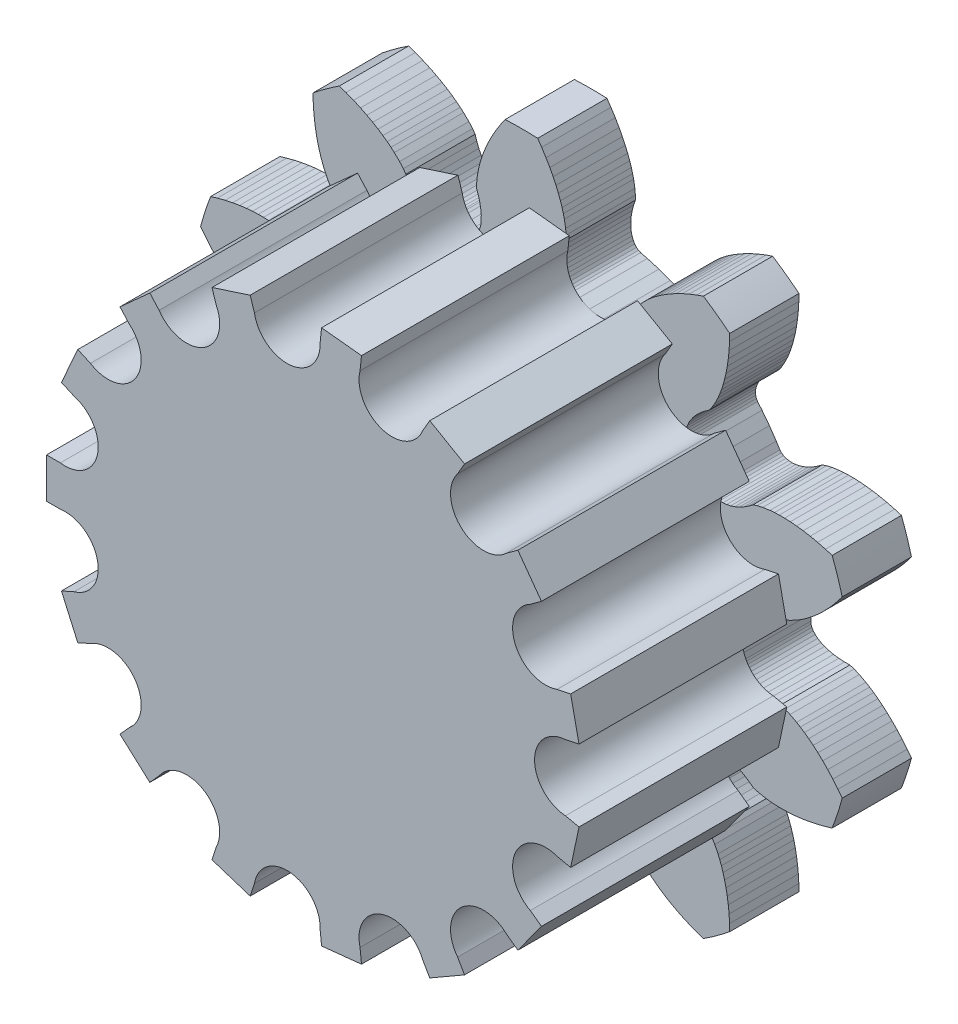
SolidWorks part; units mm, degrees
ref_plane "Front Plane" through (0, 0, 0) normal (0, 0, 1) x (1, 0, 0)
ref_plane "Top Plane" through (0, 0, 0) normal (0, 1, 0) x (1, 0, 0)
ref_plane "Right Plane" through (0, 0, 0) normal (1, 0, 0) x (0, 0, -1)
sketch "Model" plane through (0, 0, 0) normal (0, 0, 1) x (1, 0, 0)
  line L0 (44.9714, -18.1936) -> (45.0072, -17.6135)
  line L1 (45.0072, -17.6135) -> (45.064, -17.0676)
  line L2 (45.064, -17.0676) -> (45.1386, -16.5586)
  line L3 (45.1386, -16.5586) -> (45.2286, -16.0837)
  line L4 (45.2286, -16.0837) -> (45.3307, -15.6464)
  line L5 (45.3307, -15.6464) -> (45.4422, -15.245)
  line L6 (45.4422, -15.245) -> (45.5601, -14.8808)
  line L7 (45.5601, -14.8808) -> (45.6817, -14.5526)
  line L8 (45.6817, -14.5526) -> (45.8046, -14.2592)
  line L9 (45.8046, -14.2592) -> (46.0415, -13.7787)
  line L10 (46.0415, -13.7787) -> (46.2493, -13.433)
  line L11 (46.2493, -13.433) -> (46.4387, -13.1745)
  line L12 (46.4387, -13.1745) -> (46.7566, -12.9496)
  line L13 (46.7566, -12.9496) -> (47.0768, -12.6883)
  line L14 (47.0768, -12.6883) -> (47.3522, -12.4243)
  line L15 (47.3522, -12.4243) -> (47.5834, -12.1609)
  line L16 (47.5834, -12.1609) -> (47.7708, -11.9014)
  line L17 (47.7708, -11.9014) -> (47.9153, -11.6488)
  line L18 (47.9153, -11.6488) -> (48.0178, -11.4063)
  line L19 (48.0178, -11.4063) -> (48.0795, -11.177)
  line L20 (48.0795, -11.177) -> (48.1017, -10.9637)
  line L21 (48.1017, -10.9637) -> (48.086, -10.7695)
  line L22 (48.086, -10.7695) -> (48.034, -10.597)
  line L23 (48.034, -10.597) -> (47.9475, -10.4489)
  line L24 (47.9475, -10.4489) -> (47.6302, -10.0694)
  line L25 (47.6302, -10.0694) -> (47.0962, -9.3752)
  line L26 (47.0962, -9.3752) -> (46.601, -8.6528)
  line L27 (46.601, -8.6528) -> (46.3381, -8.2337)
  line L28 (46.3381, -8.2337) -> (46.224, -8.1057)
  line L29 (46.224, -8.1057) -> (46.076, -8.0029)
  line L30 (46.076, -8.0029) -> (45.8961, -7.9279)
  line L31 (45.8961, -7.9279) -> (45.6864, -7.8832)
  line L32 (45.6864, -7.8832) -> (45.4493, -7.871)
  line L33 (45.4493, -7.871) -> (45.187, -7.8936)
  line L34 (45.187, -7.8936) -> (44.9021, -7.9529)
  line L35 (44.9021, -7.9529) -> (44.5973, -8.051)
  line L36 (44.5973, -8.051) -> (44.2754, -8.1894)
  line L37 (44.2754, -8.1894) -> (43.9392, -8.3698)
  line L38 (43.9392, -8.3698) -> (43.5918, -8.5936)
  line L39 (43.5918, -8.5936) -> (43.2796, -8.8264)
  line L40 (43.2796, -8.8264) -> (42.9752, -8.9266)
  line L41 (42.9752, -8.9266) -> (42.5822, -9.0175)
  line L42 (42.5822, -9.0175) -> (42.052, -9.0943)
  line L43 (42.052, -9.0943) -> (41.735, -9.1205)
  line L44 (41.735, -9.1205) -> (41.3854, -9.1348)
  line L45 (41.3854, -9.1348) -> (41.0026, -9.1343)
  line L46 (41.0026, -9.1343) -> (40.5863, -9.1164)
  line L47 (40.5863, -9.1164) -> (40.1389, -9.0783)
  line L48 (40.1389, -9.0783) -> (39.6594, -9.0172)
  line L49 (39.6594, -9.0172) -> (39.1523, -8.9308)
  line L50 (39.1523, -8.9308) -> (38.6155, -8.8161)
  line L51 (38.6155, -8.8161) -> (38.0528, -8.671)
  line L52 (38.0528, -8.671) -> (37.565, -8.5243)
  line L53 (36.8392, -6.2906) -> (37.1476, -5.8853)
  line L54 (37.1476, -5.8853) -> (37.5176, -5.4371)
  line L55 (37.5176, -5.4371) -> (37.8845, -5.0288)
  line L56 (37.8845, -5.0288) -> (38.244, -4.6608)
  line L57 (38.244, -4.6608) -> (38.596, -4.3295)
  line L58 (38.596, -4.3295) -> (38.9355, -4.0358)
  line L59 (38.9355, -4.0358) -> (39.2618, -3.7766)
  line L60 (39.2618, -3.7766) -> (39.5712, -3.5512)
  line L61 (39.5712, -3.5512) -> (39.8624, -3.3572)
  line L62 (39.8624, -3.3572) -> (40.1343, -3.1921)
  line L63 (40.1343, -3.1921) -> (40.6084, -2.9426)
  line L64 (40.6084, -2.9426) -> (40.9797, -2.7851)
  line L65 (40.9797, -2.7851) -> (41.2849, -2.6873)
  line L66 (41.2849, -2.6873) -> (41.6743, -2.6921)
  line L67 (41.6743, -2.6921) -> (42.0869, -2.669)
  line L68 (42.0869, -2.669) -> (42.4649, -2.6173)
  line L69 (42.4649, -2.6173) -> (42.8067, -2.5401)
  line L70 (42.8067, -2.5401) -> (43.1109, -2.4403)
  line L71 (43.1109, -2.4403) -> (43.3763, -2.3209)
  line L72 (43.3763, -2.3209) -> (43.6018, -2.1849)
  line L73 (43.6018, -2.1849) -> (43.7865, -2.0357)
  line L74 (43.7865, -2.0357) -> (43.9298, -1.8762)
  line L75 (43.9298, -1.8762) -> (44.0312, -1.7098)
  line L76 (44.0312, -1.7098) -> (44.0905, -1.5397)
  line L77 (44.0905, -1.5397) -> (44.1076, -1.369)
  line L78 (44.1076, -1.369) -> (44.074, -0.8755)
  line L79 (44.074, -0.8755) -> (44.05, 0)
  line L80 (44.05, 0) -> (44.074, 0.8755)
  line L81 (44.074, 0.8755) -> (44.1076, 1.369)
  line L82 (44.1076, 1.369) -> (44.0905, 1.5397)
  line L83 (44.0905, 1.5397) -> (44.0312, 1.7098)
  line L84 (44.0312, 1.7098) -> (43.9298, 1.8762)
  line L85 (43.9298, 1.8762) -> (43.7865, 2.0357)
  line L86 (43.7865, 2.0357) -> (43.6018, 2.1849)
  line L87 (43.6018, 2.1849) -> (43.3763, 2.3209)
  line L88 (43.3763, 2.3209) -> (43.1109, 2.4403)
  line L89 (43.1109, 2.4403) -> (42.8067, 2.5401)
  line L90 (42.8067, 2.5401) -> (42.4649, 2.6173)
  line L91 (42.4649, 2.6173) -> (42.0869, 2.669)
  line L92 (42.0869, 2.669) -> (41.6743, 2.6921)
  line L93 (41.6743, 2.6921) -> (41.2849, 2.6873)
  line L94 (41.2849, 2.6873) -> (40.9797, 2.7851)
  line L95 (40.9797, 2.7851) -> (40.6084, 2.9426)
  line L96 (40.6084, 2.9426) -> (40.1343, 3.1921)
  line L97 (40.1343, 3.1921) -> (39.8624, 3.3572)
  line L98 (39.8624, 3.3572) -> (39.5712, 3.5512)
  line L99 (39.5712, 3.5512) -> (39.2618, 3.7766)
  line L100 (39.2618, 3.7766) -> (38.9355, 4.0358)
  line L101 (38.9355, 4.0358) -> (38.596, 4.3295)
  line L102 (38.596, 4.3295) -> (38.244, 4.6608)
  line L103 (38.244, 4.6608) -> (37.8845, 5.0288)
  line L104 (37.8845, 5.0288) -> (37.5176, 5.4371)
  line L105 (37.5176, 5.4371) -> (37.1476, 5.8853)
  line L106 (37.1476, 5.8853) -> (36.8392, 6.2906)
  line L107 (37.565, 8.5243) -> (38.0528, 8.671)
  line L108 (38.0528, 8.671) -> (38.6155, 8.8161)
  line L109 (38.6155, 8.8161) -> (39.1523, 8.9308)
  line L110 (39.1523, 8.9308) -> (39.6594, 9.0172)
  line L111 (39.6594, 9.0172) -> (40.1389, 9.0783)
  line L112 (40.1389, 9.0783) -> (40.5863, 9.1164)
  line L113 (40.5863, 9.1164) -> (41.0026, 9.1343)
  line L114 (41.0026, 9.1343) -> (41.3854, 9.1348)
  line L115 (41.3854, 9.1348) -> (41.735, 9.1205)
  line L116 (41.735, 9.1205) -> (42.052, 9.0943)
  line L117 (42.052, 9.0943) -> (42.5822, 9.0175)
  line L118 (42.5822, 9.0175) -> (42.9752, 8.9266)
  line L119 (42.9752, 8.9266) -> (43.2796, 8.8264)
  line L120 (43.2796, 8.8264) -> (43.5918, 8.5936)
  line L121 (43.5918, 8.5936) -> (43.9392, 8.3698)
  line L122 (43.9392, 8.3698) -> (44.2754, 8.1894)
  line L123 (44.2754, 8.1894) -> (44.5973, 8.051)
  line L124 (44.5973, 8.051) -> (44.9021, 7.9529)
  line L125 (44.9021, 7.9529) -> (45.187, 7.8936)
  line L126 (45.187, 7.8936) -> (45.4493, 7.871)
  line L127 (45.4493, 7.871) -> (45.6864, 7.8832)
  line L128 (45.6864, 7.8832) -> (45.8961, 7.9279)
  line L129 (45.8961, 7.9279) -> (46.076, 8.0029)
  line L130 (46.076, 8.0029) -> (46.224, 8.1057)
  line L131 (46.224, 8.1057) -> (46.3381, 8.2337)
  line L132 (46.3381, 8.2337) -> (46.601, 8.6528)
  line L133 (46.601, 8.6528) -> (47.0962, 9.3752)
  line L134 (47.0962, 9.3752) -> (47.6302, 10.0694)
  line L135 (47.6302, 10.0694) -> (47.9475, 10.4489)
  line L136 (47.9475, 10.4489) -> (48.034, 10.597)
  line L137 (48.034, 10.597) -> (48.086, 10.7695)
  line L138 (48.086, 10.7695) -> (48.1017, 10.9637)
  line L139 (48.1017, 10.9637) -> (48.0795, 11.177)
  line L140 (48.0795, 11.177) -> (48.0178, 11.4063)
  line L141 (48.0178, 11.4063) -> (47.9153, 11.6488)
  line L142 (47.9153, 11.6488) -> (47.7708, 11.9014)
  line L143 (47.7708, 11.9014) -> (47.5834, 12.1609)
  line L144 (47.5834, 12.1609) -> (47.3522, 12.4243)
  line L145 (47.3522, 12.4243) -> (47.0768, 12.6883)
  line L146 (47.0768, 12.6883) -> (46.7566, 12.9496)
  line L147 (46.7566, 12.9496) -> (46.4387, 13.1745)
  line L148 (46.4387, 13.1745) -> (46.2493, 13.433)
  line L149 (46.2493, 13.433) -> (46.0415, 13.7787)
  line L150 (46.0415, 13.7787) -> (45.8046, 14.2592)
  line L151 (45.8046, 14.2592) -> (45.6817, 14.5526)
  line L152 (45.6817, 14.5526) -> (45.5601, 14.8808)
  line L153 (45.5601, 14.8808) -> (45.4422, 15.245)
  line L154 (45.4422, 15.245) -> (45.3307, 15.6464)
  line L155 (45.3307, 15.6464) -> (45.2286, 16.0837)
  line L156 (45.2286, 16.0837) -> (45.1386, 16.5586)
  line L157 (45.1386, 16.5586) -> (45.064, 17.0676)
  line L158 (45.064, 17.0676) -> (45.0072, 17.6135)
  line L159 (45.0072, 17.6135) -> (44.9714, 18.1936)
  line L160 (44.9714, 18.1936) -> (44.9601, 18.7028)
  line L161 (46.8602, 20.0833) -> (47.341, 19.9152)
  line L162 (47.341, 19.9152) -> (47.8816, 19.7019)
  line L163 (47.8816, 19.7019) -> (48.3833, 19.4792)
  line L164 (48.3833, 19.4792) -> (48.8443, 19.2509)
  line L165 (48.8443, 19.2509) -> (49.2681, 19.0186)
  line L166 (49.2681, 19.0186) -> (49.6525, 18.7864)
  line L167 (49.6525, 18.7864) -> (49.9998, 18.5562)
  line L168 (49.9998, 18.5562) -> (50.3097, 18.3316)
  line L169 (50.3097, 18.3316) -> (50.5842, 18.1146)
  line L170 (50.5842, 18.1146) -> (50.8253, 17.907)
  line L171 (50.8253, 17.907) -> (51.2091, 17.5332)
  line L172 (51.2091, 17.5332) -> (51.4736, 17.2287)
  line L173 (51.4736, 17.2287) -> (51.6609, 16.9687)
  line L174 (51.6609, 16.9687) -> (51.7767, 16.5968)
  line L175 (51.7767, 16.5968) -> (51.9262, 16.2116)
  line L176 (51.9262, 16.2116) -> (52.0921, 15.8681)
  line L177 (52.0921, 15.8681) -> (52.2712, 15.5668)
  line L178 (52.2712, 15.5668) -> (52.4601, 15.3084)
  line L179 (52.4601, 15.3084) -> (52.6557, 15.0929)
  line L180 (52.6557, 15.0929) -> (52.8547, 14.9205)
  line L181 (52.8547, 14.9205) -> (53.0537, 14.7909)
  line L182 (53.0537, 14.7909) -> (53.2496, 14.7039)
  line L183 (53.2496, 14.7039) -> (53.4392, 14.6588)
  line L184 (53.4392, 14.6588) -> (53.6194, 14.655)
  line L185 (53.6194, 14.655) -> (53.7869, 14.6915)
  line L186 (53.7869, 14.6915) -> (54.2459, 14.876)
  line L187 (54.2459, 14.876) -> (55.0712, 15.1694)
  line L188 (55.0712, 15.1694) -> (55.9113, 15.4171)
  line L189 (55.9113, 15.4171) -> (56.391, 15.5376)
  line L190 (56.391, 15.5376) -> (56.548, 15.6066)
  line L191 (56.548, 15.6066) -> (56.6915, 15.7156)
  line L192 (56.6915, 15.7156) -> (56.8184, 15.8635)
  line L193 (56.8184, 15.8635) -> (56.9258, 16.049)
  line L194 (56.9258, 16.049) -> (57.0107, 16.2708)
  line L195 (57.0107, 16.2708) -> (57.0703, 16.5273)
  line L196 (57.0703, 16.5273) -> (57.1018, 16.8165)
  line L197 (57.1018, 16.8165) -> (57.1028, 17.1367)
  line L198 (57.1028, 17.1367) -> (57.0706, 17.4857)
  line L199 (57.0706, 17.4857) -> (57.0029, 17.8611)
  line L200 (57.0029, 17.8611) -> (56.8974, 18.2607)
  line L201 (56.8974, 18.2607) -> (56.7725, 18.6296)
  line L202 (56.7725, 18.6296) -> (56.7712, 18.95)
  line L203 (56.7712, 18.95) -> (56.8063, 19.3518)
  line L204 (56.8063, 19.3518) -> (56.897, 19.8798)
  line L205 (56.897, 19.8798) -> (56.97, 20.1894)
  line L206 (56.97, 20.1894) -> (57.0646, 20.5264)
  line L207 (57.0646, 20.5264) -> (57.1833, 20.8903)
  line L208 (57.1833, 20.8903) -> (57.329, 21.2806)
  line L209 (57.329, 21.2806) -> (57.5034, 21.6944)
  line L210 (57.5034, 21.6944) -> (57.7097, 22.1315)
  line L211 (57.7097, 22.1315) -> (57.9486, 22.5871)
  line L212 (57.9486, 22.5871) -> (58.2236, 23.0622)
  line L213 (58.2236, 23.0622) -> (58.5355, 23.5525)
  line L214 (58.5355, 23.5525) -> (58.8257, 23.9711)
  line L215 (61.1743, 23.9711) -> (61.4645, 23.5525)
  line L216 (61.4645, 23.5525) -> (61.7764, 23.0622)
  line L217 (61.7764, 23.0622) -> (62.0514, 22.5871)
  line L218 (62.0514, 22.5871) -> (62.2903, 22.1315)
  line L219 (62.2903, 22.1315) -> (62.4966, 21.6944)
  line L220 (62.4966, 21.6944) -> (62.671, 21.2806)
  line L221 (62.671, 21.2806) -> (62.8167, 20.8903)
  line L222 (62.8167, 20.8903) -> (62.9354, 20.5264)
  line L223 (62.9354, 20.5264) -> (63.03, 20.1894)
  line L224 (63.03, 20.1894) -> (63.103, 19.8798)
  line L225 (63.103, 19.8798) -> (63.1937, 19.3518)
  line L226 (63.1937, 19.3518) -> (63.2288, 18.95)
  line L227 (63.2288, 18.95) -> (63.2275, 18.6296)
  line L228 (63.2275, 18.6296) -> (63.1026, 18.2607)
  line L229 (63.1026, 18.2607) -> (62.9971, 17.8611)
  line L230 (62.9971, 17.8611) -> (62.9294, 17.4857)
  line L231 (62.9294, 17.4857) -> (62.8972, 17.1367)
  line L232 (62.8972, 17.1367) -> (62.8982, 16.8165)
  line L233 (62.8982, 16.8165) -> (62.9297, 16.5273)
  line L234 (62.9297, 16.5273) -> (62.9893, 16.2708)
  line L235 (62.9893, 16.2708) -> (63.0742, 16.049)
  line L236 (63.0742, 16.049) -> (63.1816, 15.8635)
  line L237 (63.1816, 15.8635) -> (63.3085, 15.7156)
  line L238 (63.3085, 15.7156) -> (63.452, 15.6066)
  line L239 (63.452, 15.6066) -> (63.609, 15.5376)
  line L240 (63.609, 15.5376) -> (64.0887, 15.4171)
  line L241 (64.0887, 15.4171) -> (64.9288, 15.1694)
  line L242 (64.9288, 15.1694) -> (65.7541, 14.876)
  line L243 (65.7541, 14.876) -> (66.2131, 14.6915)
  line L244 (66.2131, 14.6915) -> (66.3806, 14.655)
  line L245 (66.3806, 14.655) -> (66.5608, 14.6588)
  line L246 (66.5608, 14.6588) -> (66.7504, 14.7039)
  line L247 (66.7504, 14.7039) -> (66.9463, 14.7909)
  line L248 (66.9463, 14.7909) -> (67.1453, 14.9205)
  line L249 (67.1453, 14.9205) -> (67.3443, 15.0929)
  line L250 (67.3443, 15.0929) -> (67.5399, 15.3084)
  line L251 (67.5399, 15.3084) -> (67.7288, 15.5668)
  line L252 (67.7288, 15.5668) -> (67.9079, 15.8681)
  line L253 (67.9079, 15.8681) -> (68.0738, 16.2116)
  line L254 (68.0738, 16.2116) -> (68.2233, 16.5968)
  line L255 (68.2233, 16.5968) -> (68.3391, 16.9687)
  line L256 (68.3391, 16.9687) -> (68.5264, 17.2287)
  line L257 (68.5264, 17.2287) -> (68.7909, 17.5332)
  line L258 (68.7909, 17.5332) -> (69.1747, 17.907)
  line L259 (69.1747, 17.907) -> (69.4158, 18.1146)
  line L260 (69.4158, 18.1146) -> (69.6903, 18.3316)
  line L261 (69.6903, 18.3316) -> (70.0002, 18.5562)
  line L262 (70.0002, 18.5562) -> (70.3475, 18.7864)
  line L263 (70.3475, 18.7864) -> (70.7319, 19.0186)
  line L264 (70.7319, 19.0186) -> (71.1557, 19.2509)
  line L265 (71.1557, 19.2509) -> (71.6167, 19.4792)
  line L266 (71.6167, 19.4792) -> (72.1184, 19.7019)
  line L267 (72.1184, 19.7019) -> (72.659, 19.9152)
  line L268 (72.659, 19.9152) -> (73.1398, 20.0833)
  line L269 (75.0399, 18.7028) -> (75.0286, 18.1936)
  line L270 (75.0286, 18.1936) -> (74.9928, 17.6135)
  line L271 (74.9928, 17.6135) -> (74.936, 17.0676)
  line L272 (74.936, 17.0676) -> (74.8614, 16.5586)
  line L273 (74.8614, 16.5586) -> (74.7714, 16.0837)
  line L274 (74.7714, 16.0837) -> (74.6693, 15.6464)
  line L275 (74.6693, 15.6464) -> (74.5578, 15.245)
  line L276 (74.5578, 15.245) -> (74.4399, 14.8808)
  line L277 (74.4399, 14.8808) -> (74.3183, 14.5526)
  line L278 (74.3183, 14.5526) -> (74.1954, 14.2592)
  line L279 (74.1954, 14.2592) -> (73.9585, 13.7787)
  line L280 (73.9585, 13.7787) -> (73.7507, 13.433)
  line L281 (73.7507, 13.433) -> (73.5613, 13.1745)
  line L282 (73.5613, 13.1745) -> (73.2434, 12.9496)
  line L283 (73.2434, 12.9496) -> (72.9232, 12.6883)
  line L284 (72.9232, 12.6883) -> (72.6478, 12.4243)
  line L285 (72.6478, 12.4243) -> (72.4166, 12.1609)
  line L286 (72.4166, 12.1609) -> (72.2292, 11.9014)
  line L287 (72.2292, 11.9014) -> (72.0847, 11.6488)
  line L288 (72.0847, 11.6488) -> (71.9822, 11.4063)
  line L289 (71.9822, 11.4063) -> (71.9205, 11.177)
  line L290 (71.9205, 11.177) -> (71.8983, 10.9637)
  line L291 (71.8983, 10.9637) -> (71.914, 10.7695)
  line L292 (71.914, 10.7695) -> (71.966, 10.597)
  line L293 (71.966, 10.597) -> (72.0525, 10.4489)
  line L294 (72.0525, 10.4489) -> (72.3698, 10.0694)
  line L295 (72.3698, 10.0694) -> (72.9038, 9.3752)
  line L296 (72.9038, 9.3752) -> (73.399, 8.6528)
  line L297 (73.399, 8.6528) -> (73.6619, 8.2337)
  line L298 (73.6619, 8.2337) -> (73.776, 8.1057)
  line L299 (73.776, 8.1057) -> (73.924, 8.0029)
  line L300 (73.924, 8.0029) -> (74.1039, 7.9279)
  line L301 (74.1039, 7.9279) -> (74.3136, 7.8832)
  line L302 (74.3136, 7.8832) -> (74.5507, 7.871)
  line L303 (74.5507, 7.871) -> (74.813, 7.8936)
  line L304 (74.813, 7.8936) -> (75.0979, 7.9529)
  line L305 (75.0979, 7.9529) -> (75.4027, 8.051)
  line L306 (75.4027, 8.051) -> (75.7246, 8.1894)
  line L307 (75.7246, 8.1894) -> (76.0608, 8.3698)
  line L308 (76.0608, 8.3698) -> (76.4082, 8.5936)
  line L309 (76.4082, 8.5936) -> (76.7204, 8.8264)
  line L310 (76.7204, 8.8264) -> (77.0248, 8.9266)
  line L311 (77.0248, 8.9266) -> (77.4178, 9.0175)
  line L312 (77.4178, 9.0175) -> (77.948, 9.0943)
  line L313 (77.948, 9.0943) -> (78.265, 9.1205)
  line L314 (78.265, 9.1205) -> (78.6146, 9.1348)
  line L315 (78.6146, 9.1348) -> (78.9974, 9.1343)
  line L316 (78.9974, 9.1343) -> (79.4137, 9.1164)
  line L317 (79.4137, 9.1164) -> (79.8611, 9.0783)
  line L318 (79.8611, 9.0783) -> (80.3406, 9.0172)
  line L319 (80.3406, 9.0172) -> (80.8477, 8.9308)
  line L320 (80.8477, 8.9308) -> (81.3845, 8.8161)
  line L321 (81.3845, 8.8161) -> (81.9472, 8.671)
  line L322 (81.9472, 8.671) -> (82.435, 8.5243)
  line L323 (83.1608, 6.2906) -> (82.8524, 5.8853)
  line L324 (82.8524, 5.8853) -> (82.4824, 5.4371)
  line L325 (82.4824, 5.4371) -> (82.1155, 5.0288)
  line L326 (82.1155, 5.0288) -> (81.756, 4.6608)
  line L327 (81.756, 4.6608) -> (81.4041, 4.3295)
  line L328 (81.4041, 4.3295) -> (81.0645, 4.0358)
  line L329 (81.0645, 4.0358) -> (80.7382, 3.7766)
  line L330 (80.7382, 3.7766) -> (80.4288, 3.5512)
  line L331 (80.4288, 3.5512) -> (80.1376, 3.3572)
  line L332 (80.1376, 3.3572) -> (79.8657, 3.1921)
  line L333 (79.8657, 3.1921) -> (79.3916, 2.9426)
  line L334 (79.3916, 2.9426) -> (79.0203, 2.7851)
  line L335 (79.0203, 2.7851) -> (78.7151, 2.6873)
  line L336 (78.7151, 2.6873) -> (78.3257, 2.6921)
  line L337 (78.3257, 2.6921) -> (77.9131, 2.669)
  line L338 (77.9131, 2.669) -> (77.5351, 2.6173)
  line L339 (77.5351, 2.6173) -> (77.1933, 2.5401)
  line L340 (77.1933, 2.5401) -> (76.8891, 2.4403)
  line L341 (76.8891, 2.4403) -> (76.6237, 2.3209)
  line L342 (76.6237, 2.3209) -> (76.3983, 2.1849)
  line L343 (76.3983, 2.1849) -> (76.2135, 2.0357)
  line L344 (76.2135, 2.0357) -> (76.0702, 1.8762)
  line L345 (76.0702, 1.8762) -> (75.9688, 1.7098)
  line L346 (75.9688, 1.7098) -> (75.9095, 1.5397)
  line L347 (75.9095, 1.5397) -> (75.8924, 1.369)
  line L348 (75.8924, 1.369) -> (75.926, 0.8755)
  line L349 (75.926, 0.8755) -> (75.95, 0)
  line L350 (75.95, 0) -> (75.926, -0.8755)
  line L351 (75.926, -0.8755) -> (75.8924, -1.369)
  line L352 (75.8924, -1.369) -> (75.9095, -1.5397)
  line L353 (75.9095, -1.5397) -> (75.9688, -1.7098)
  line L354 (75.9688, -1.7098) -> (76.0702, -1.8762)
  line L355 (76.0702, -1.8762) -> (76.2135, -2.0357)
  line L356 (76.2135, -2.0357) -> (76.3983, -2.1849)
  line L357 (76.3983, -2.1849) -> (76.6237, -2.3209)
  line L358 (76.6237, -2.3209) -> (76.8891, -2.4403)
  line L359 (76.8891, -2.4403) -> (77.1933, -2.5401)
  line L360 (77.1933, -2.5401) -> (77.5351, -2.6173)
  line L361 (77.5351, -2.6173) -> (77.9131, -2.669)
  line L362 (77.9131, -2.669) -> (78.3257, -2.6921)
  line L363 (78.3257, -2.6921) -> (78.7151, -2.6873)
  line L364 (78.7151, -2.6873) -> (79.0203, -2.7851)
  line L365 (79.0203, -2.7851) -> (79.3916, -2.9426)
  line L366 (79.3916, -2.9426) -> (79.8657, -3.1921)
  line L367 (79.8657, -3.1921) -> (80.1376, -3.3572)
  line L368 (80.1376, -3.3572) -> (80.4288, -3.5512)
  line L369 (80.4288, -3.5512) -> (80.7382, -3.7766)
  line L370 (80.7382, -3.7766) -> (81.0645, -4.0358)
  line L371 (81.0645, -4.0358) -> (81.4041, -4.3295)
  line L372 (81.4041, -4.3295) -> (81.756, -4.6608)
  line L373 (81.756, -4.6608) -> (82.1155, -5.0288)
  line L374 (82.1155, -5.0288) -> (82.4824, -5.4371)
  line L375 (82.4824, -5.4371) -> (82.8524, -5.8853)
  line L376 (82.8524, -5.8853) -> (83.1608, -6.2906)
  line L377 (82.435, -8.5243) -> (81.9472, -8.671)
  line L378 (81.9472, -8.671) -> (81.3845, -8.8161)
  line L379 (81.3845, -8.8161) -> (80.8477, -8.9308)
  line L380 (80.8477, -8.9308) -> (80.3406, -9.0172)
  line L381 (80.3406, -9.0172) -> (79.8611, -9.0783)
  line L382 (79.8611, -9.0783) -> (79.4137, -9.1164)
  line L383 (79.4137, -9.1164) -> (78.9974, -9.1343)
  line L384 (78.9974, -9.1343) -> (78.6146, -9.1348)
  line L385 (78.6146, -9.1348) -> (78.265, -9.1205)
  line L386 (78.265, -9.1205) -> (77.948, -9.0943)
  line L387 (77.948, -9.0943) -> (77.4178, -9.0175)
  line L388 (77.4178, -9.0175) -> (77.0248, -8.9266)
  line L389 (77.0248, -8.9266) -> (76.7204, -8.8264)
  line L390 (76.7204, -8.8264) -> (76.4082, -8.5936)
  line L391 (76.4082, -8.5936) -> (76.0608, -8.3698)
  line L392 (76.0608, -8.3698) -> (75.7246, -8.1894)
  line L393 (75.7246, -8.1894) -> (75.4027, -8.051)
  line L394 (75.4027, -8.051) -> (75.0979, -7.9529)
  line L395 (75.0979, -7.9529) -> (74.813, -7.8936)
  line L396 (74.813, -7.8936) -> (74.5507, -7.871)
  line L397 (74.5507, -7.871) -> (74.3136, -7.8832)
  line L398 (74.3136, -7.8832) -> (74.1039, -7.9279)
  line L399 (74.1039, -7.9279) -> (73.924, -8.0029)
  line L400 (73.924, -8.0029) -> (73.776, -8.1057)
  line L401 (73.776, -8.1057) -> (73.6619, -8.2337)
  line L402 (73.6619, -8.2337) -> (73.399, -8.6528)
  line L403 (73.399, -8.6528) -> (72.9038, -9.3752)
  line L404 (72.9038, -9.3752) -> (72.3698, -10.0694)
  line L405 (72.3698, -10.0694) -> (72.0525, -10.4489)
  line L406 (72.0525, -10.4489) -> (71.966, -10.597)
  line L407 (71.966, -10.597) -> (71.914, -10.7695)
  line L408 (71.914, -10.7695) -> (71.8983, -10.9637)
  line L409 (71.8983, -10.9637) -> (71.9205, -11.177)
  line L410 (71.9205, -11.177) -> (71.9822, -11.4063)
  line L411 (71.9822, -11.4063) -> (72.0847, -11.6488)
  line L412 (72.0847, -11.6488) -> (72.2292, -11.9014)
  line L413 (72.2292, -11.9014) -> (72.4166, -12.1609)
  line L414 (72.4166, -12.1609) -> (72.6478, -12.4243)
  line L415 (72.6478, -12.4243) -> (72.9232, -12.6883)
  line L416 (72.9232, -12.6883) -> (73.2434, -12.9496)
  line L417 (73.2434, -12.9496) -> (73.5613, -13.1745)
  line L418 (73.5613, -13.1745) -> (73.7507, -13.433)
  line L419 (73.7507, -13.433) -> (73.9585, -13.7787)
  line L420 (73.9585, -13.7787) -> (74.1954, -14.2592)
  line L421 (74.1954, -14.2592) -> (74.3183, -14.5526)
  line L422 (74.3183, -14.5526) -> (74.4399, -14.8808)
  line L423 (74.4399, -14.8808) -> (74.5578, -15.245)
  line L424 (74.5578, -15.245) -> (74.6693, -15.6464)
  line L425 (74.6693, -15.6464) -> (74.7714, -16.0837)
  line L426 (74.7714, -16.0837) -> (74.8614, -16.5586)
  line L427 (74.8614, -16.5586) -> (74.936, -17.0676)
  line L428 (74.936, -17.0676) -> (74.9928, -17.6135)
  line L429 (74.9928, -17.6135) -> (75.0286, -18.1936)
  line L430 (75.0286, -18.1936) -> (75.0399, -18.7028)
  line L431 (73.1398, -20.0833) -> (72.659, -19.9152)
  line L432 (72.659, -19.9152) -> (72.1184, -19.7019)
  line L433 (72.1184, -19.7019) -> (71.6167, -19.4792)
  line L434 (71.6167, -19.4792) -> (71.1557, -19.2509)
  line L435 (71.1557, -19.2509) -> (70.7319, -19.0186)
  line L436 (70.7319, -19.0186) -> (70.3475, -18.7864)
  line L437 (70.3475, -18.7864) -> (70.0002, -18.5562)
  line L438 (70.0002, -18.5562) -> (69.6903, -18.3316)
  line L439 (69.6903, -18.3316) -> (69.4158, -18.1146)
  line L440 (69.4158, -18.1146) -> (69.1747, -17.907)
  line L441 (69.1747, -17.907) -> (68.7909, -17.5332)
  line L442 (68.7909, -17.5332) -> (68.5264, -17.2287)
  line L443 (68.5264, -17.2287) -> (68.3391, -16.9687)
  line L444 (68.3391, -16.9687) -> (68.2233, -16.5968)
  line L445 (68.2233, -16.5968) -> (68.0738, -16.2116)
  line L446 (68.0738, -16.2116) -> (67.9079, -15.8681)
  line L447 (67.9079, -15.8681) -> (67.7288, -15.5668)
  line L448 (67.7288, -15.5668) -> (67.5399, -15.3084)
  line L449 (67.5399, -15.3084) -> (67.3443, -15.0929)
  line L450 (67.3443, -15.0929) -> (67.1453, -14.9205)
  line L451 (67.1453, -14.9205) -> (66.9463, -14.7909)
  line L452 (66.9463, -14.7909) -> (66.7504, -14.7039)
  line L453 (66.7504, -14.7039) -> (66.5608, -14.6588)
  line L454 (66.5608, -14.6588) -> (66.3806, -14.655)
  line L455 (66.3806, -14.655) -> (66.2131, -14.6915)
  line L456 (66.2131, -14.6915) -> (65.7541, -14.876)
  line L457 (65.7541, -14.876) -> (64.9288, -15.1694)
  line L458 (64.9288, -15.1694) -> (64.0887, -15.4171)
  line L459 (64.0887, -15.4171) -> (63.609, -15.5376)
  line L460 (63.609, -15.5376) -> (63.452, -15.6066)
  line L461 (63.452, -15.6066) -> (63.3085, -15.7156)
  line L462 (63.3085, -15.7156) -> (63.1816, -15.8635)
  line L463 (63.1816, -15.8635) -> (63.0742, -16.049)
  line L464 (63.0742, -16.049) -> (62.9893, -16.2708)
  line L465 (62.9893, -16.2708) -> (62.9297, -16.5273)
  line L466 (62.9297, -16.5273) -> (62.8982, -16.8165)
  line L467 (62.8982, -16.8165) -> (62.8972, -17.1367)
  line L468 (62.8972, -17.1367) -> (62.9294, -17.4857)
  line L469 (62.9294, -17.4857) -> (62.9971, -17.8611)
  line L470 (62.9971, -17.8611) -> (63.1026, -18.2607)
  line L471 (63.1026, -18.2607) -> (63.2275, -18.6296)
  line L472 (63.2275, -18.6296) -> (63.2288, -18.95)
  line L473 (63.2288, -18.95) -> (63.1937, -19.3518)
  line L474 (63.1937, -19.3518) -> (63.103, -19.8798)
  line L475 (63.103, -19.8798) -> (63.03, -20.1894)
  line L476 (63.03, -20.1894) -> (62.9354, -20.5264)
  line L477 (62.9354, -20.5264) -> (62.8167, -20.8903)
  line L478 (62.8167, -20.8903) -> (62.671, -21.2806)
  line L479 (62.671, -21.2806) -> (62.4966, -21.6944)
  line L480 (62.4966, -21.6944) -> (62.2903, -22.1315)
  line L481 (62.2903, -22.1315) -> (62.0514, -22.5871)
  line L482 (62.0514, -22.5871) -> (61.7764, -23.0622)
  line L483 (61.7764, -23.0622) -> (61.4645, -23.5525)
  line L484 (61.4645, -23.5525) -> (61.1743, -23.9711)
  line L485 (58.8257, -23.9711) -> (58.5355, -23.5525)
  line L486 (58.5355, -23.5525) -> (58.2236, -23.0622)
  line L487 (58.2236, -23.0622) -> (57.9486, -22.5871)
  line L488 (57.9486, -22.5871) -> (57.7097, -22.1315)
  line L489 (57.7097, -22.1315) -> (57.5034, -21.6944)
  line L490 (57.5034, -21.6944) -> (57.329, -21.2806)
  line L491 (57.329, -21.2806) -> (57.1833, -20.8903)
  line L492 (57.1833, -20.8903) -> (57.0646, -20.5264)
  line L493 (57.0646, -20.5264) -> (56.97, -20.1894)
  line L494 (56.97, -20.1894) -> (56.897, -19.8798)
  line L495 (56.897, -19.8798) -> (56.8063, -19.3518)
  line L496 (56.8063, -19.3518) -> (56.7712, -18.95)
  line L497 (56.7712, -18.95) -> (56.7725, -18.6296)
  line L498 (56.7725, -18.6296) -> (56.8974, -18.2607)
  line L499 (56.8974, -18.2607) -> (57.0029, -17.8611)
  line L500 (57.0029, -17.8611) -> (57.0706, -17.4857)
  line L501 (57.0706, -17.4857) -> (57.1028, -17.1367)
  line L502 (57.1028, -17.1367) -> (57.1018, -16.8165)
  line L503 (57.1018, -16.8165) -> (57.0703, -16.5273)
  line L504 (57.0703, -16.5273) -> (57.0107, -16.2708)
  line L505 (57.0107, -16.2708) -> (56.9258, -16.049)
  line L506 (56.9258, -16.049) -> (56.8184, -15.8635)
  line L507 (56.8184, -15.8635) -> (56.6915, -15.7156)
  line L508 (56.6915, -15.7156) -> (56.548, -15.6066)
  line L509 (56.548, -15.6066) -> (56.391, -15.5376)
  line L510 (56.391, -15.5376) -> (55.9113, -15.4171)
  line L511 (55.9113, -15.4171) -> (55.0712, -15.1694)
  line L512 (55.0712, -15.1694) -> (54.2459, -14.876)
  line L513 (54.2459, -14.876) -> (53.7869, -14.6915)
  line L514 (53.7869, -14.6915) -> (53.6194, -14.655)
  line L515 (53.6194, -14.655) -> (53.4392, -14.6588)
  line L516 (53.4392, -14.6588) -> (53.2496, -14.7039)
  line L517 (53.2496, -14.7039) -> (53.0537, -14.7909)
  line L518 (53.0537, -14.7909) -> (52.8547, -14.9205)
  line L519 (52.8547, -14.9205) -> (52.6557, -15.0929)
  line L520 (52.6557, -15.0929) -> (52.4601, -15.3084)
  line L521 (52.4601, -15.3084) -> (52.2712, -15.5668)
  line L522 (52.2712, -15.5668) -> (52.0921, -15.8681)
  line L523 (52.0921, -15.8681) -> (51.9262, -16.2116)
  line L524 (51.9262, -16.2116) -> (51.7767, -16.5968)
  line L525 (51.7767, -16.5968) -> (51.6609, -16.9687)
  line L526 (51.6609, -16.9687) -> (51.4736, -17.2287)
  line L527 (51.4736, -17.2287) -> (51.2091, -17.5332)
  line L528 (51.2091, -17.5332) -> (50.8253, -17.907)
  line L529 (50.8253, -17.907) -> (50.5842, -18.1146)
  line L530 (50.5842, -18.1146) -> (50.3097, -18.3316)
  line L531 (50.3097, -18.3316) -> (49.9998, -18.5562)
  line L532 (49.9998, -18.5562) -> (49.6525, -18.7864)
  line L533 (49.6525, -18.7864) -> (49.2681, -19.0186)
  line L534 (49.2681, -19.0186) -> (48.8443, -19.2509)
  line L535 (48.8443, -19.2509) -> (48.3833, -19.4792)
  line L536 (48.3833, -19.4792) -> (47.8816, -19.7019)
  line L537 (47.8816, -19.7019) -> (47.341, -19.9152)
  line L538 (47.341, -19.9152) -> (46.8602, -20.0833)
  line L539 (44.9601, -18.7028) -> (44.9714, -18.1936)
  line L540 (44.9714, -18.1936) -> (45.0072, -17.6135)
  line L541 (45.0072, -17.6135) -> (45.064, -17.0676)
  line L542 (45.064, -17.0676) -> (45.1386, -16.5586)
  line L543 (45.1386, -16.5586) -> (45.2286, -16.0837)
  line L544 (45.2286, -16.0837) -> (45.3307, -15.6464)
  line L545 (45.3307, -15.6464) -> (45.4422, -15.245)
  line L546 (45.4422, -15.245) -> (45.5601, -14.8808)
  line L547 (45.5601, -14.8808) -> (45.6817, -14.5526)
  line L548 (45.6817, -14.5526) -> (45.8046, -14.2592)
  line L549 (45.8046, -14.2592) -> (46.0415, -13.7787)
  line L550 (46.0415, -13.7787) -> (46.2493, -13.433)
  line L551 (46.2493, -13.433) -> (46.4387, -13.1745)
  line L552 (46.4387, -13.1745) -> (46.7566, -12.9496)
  line L553 (46.7566, -12.9496) -> (47.0768, -12.6883)
  line L554 (47.0768, -12.6883) -> (47.3522, -12.4243)
  line L555 (47.3522, -12.4243) -> (47.5834, -12.1609)
  line L556 (47.5834, -12.1609) -> (47.7708, -11.9014)
  line L557 (47.7708, -11.9014) -> (47.9153, -11.6488)
  line L558 (47.9153, -11.6488) -> (48.0178, -11.4063)
  line L559 (48.0178, -11.4063) -> (48.0795, -11.177)
  line L560 (48.0795, -11.177) -> (48.1017, -10.9637)
  line L561 (48.1017, -10.9637) -> (48.086, -10.7695)
  line L562 (48.086, -10.7695) -> (48.034, -10.597)
  line L563 (48.034, -10.597) -> (47.9475, -10.4489)
  line L564 (47.9475, -10.4489) -> (47.6302, -10.0694)
  line L565 (47.6302, -10.0694) -> (47.0962, -9.3752)
  line L566 (47.0962, -9.3752) -> (46.601, -8.6528)
  line L567 (46.601, -8.6528) -> (46.3381, -8.2337)
  line L568 (46.3381, -8.2337) -> (46.224, -8.1057)
  line L569 (46.224, -8.1057) -> (46.076, -8.0029)
  line L570 (46.076, -8.0029) -> (45.8961, -7.9279)
  line L571 (45.8961, -7.9279) -> (45.6864, -7.8832)
  line L572 (45.6864, -7.8832) -> (45.4493, -7.871)
  line L573 (45.4493, -7.871) -> (45.187, -7.8936)
  line L574 (45.187, -7.8936) -> (44.9021, -7.9529)
  line L575 (44.9021, -7.9529) -> (44.5973, -8.051)
  line L576 (44.5973, -8.051) -> (44.2754, -8.1894)
  line L577 (44.2754, -8.1894) -> (43.9392, -8.3698)
  line L578 (43.9392, -8.3698) -> (43.5918, -8.5936)
  line L579 (43.5918, -8.5936) -> (43.2796, -8.8264)
  line L580 (43.2796, -8.8264) -> (42.9752, -8.9266)
  line L581 (42.9752, -8.9266) -> (42.5822, -9.0175)
  line L582 (42.5822, -9.0175) -> (42.052, -9.0943)
  line L583 (42.052, -9.0943) -> (41.735, -9.1205)
  line L584 (41.735, -9.1205) -> (41.3854, -9.1348)
  line L585 (41.3854, -9.1348) -> (41.0026, -9.1343)
  line L586 (41.0026, -9.1343) -> (40.5863, -9.1164)
  line L587 (40.5863, -9.1164) -> (40.1389, -9.0783)
  line L588 (40.1389, -9.0783) -> (39.6594, -9.0172)
  line L589 (39.6594, -9.0172) -> (39.1523, -8.9308)
  line L590 (39.1523, -8.9308) -> (38.6155, -8.8161)
  line L591 (38.6155, -8.8161) -> (38.0528, -8.671)
  line L592 (38.0528, -8.671) -> (37.565, -8.5243)
  line L593 (36.8392, -6.2906) -> (37.1476, -5.8853)
  line L594 (37.1476, -5.8853) -> (37.5176, -5.4371)
  line L595 (37.5176, -5.4371) -> (37.8845, -5.0288)
  line L596 (37.8845, -5.0288) -> (38.244, -4.6608)
  line L597 (38.244, -4.6608) -> (38.596, -4.3295)
  line L598 (38.596, -4.3295) -> (38.9355, -4.0358)
  line L599 (38.9355, -4.0358) -> (39.2618, -3.7766)
  line L600 (39.2618, -3.7766) -> (39.5712, -3.5512)
  line L601 (39.5712, -3.5512) -> (39.8624, -3.3572)
  line L602 (39.8624, -3.3572) -> (40.1343, -3.1921)
  line L603 (40.1343, -3.1921) -> (40.6084, -2.9426)
  line L604 (40.6084, -2.9426) -> (40.9797, -2.7851)
  line L605 (40.9797, -2.7851) -> (41.2849, -2.6873)
  line L606 (41.2849, -2.6873) -> (41.6743, -2.6921)
  line L607 (41.6743, -2.6921) -> (42.0869, -2.669)
  line L608 (42.0869, -2.669) -> (42.4649, -2.6173)
  line L609 (42.4649, -2.6173) -> (42.8067, -2.5401)
  line L610 (42.8067, -2.5401) -> (43.1109, -2.4403)
  line L611 (43.1109, -2.4403) -> (43.3763, -2.3209)
  line L612 (43.3763, -2.3209) -> (43.6018, -2.1849)
  line L613 (43.6018, -2.1849) -> (43.7865, -2.0357)
  line L614 (43.7865, -2.0357) -> (43.9298, -1.8762)
  line L615 (43.9298, -1.8762) -> (44.0312, -1.7098)
  line L616 (44.0312, -1.7098) -> (44.0905, -1.5397)
  line L617 (44.0905, -1.5397) -> (44.1076, -1.369)
  line L618 (44.1076, -1.369) -> (44.074, -0.8755)
  line L619 (44.074, -0.8755) -> (44.05, 0)
  line L620 (44.05, 0) -> (44.074, 0.8755)
  line L621 (44.074, 0.8755) -> (44.1076, 1.369)
  line L622 (44.1076, 1.369) -> (44.0905, 1.5397)
  line L623 (44.0905, 1.5397) -> (44.0312, 1.7098)
  line L624 (44.0312, 1.7098) -> (43.9298, 1.8762)
  line L625 (43.9298, 1.8762) -> (43.7865, 2.0357)
  line L626 (43.7865, 2.0357) -> (43.6018, 2.1849)
  line L627 (43.6018, 2.1849) -> (43.3763, 2.3209)
  line L628 (43.3763, 2.3209) -> (43.1109, 2.4403)
  line L629 (43.1109, 2.4403) -> (42.8067, 2.5401)
  line L630 (42.8067, 2.5401) -> (42.4649, 2.6173)
  line L631 (42.4649, 2.6173) -> (42.0869, 2.669)
  line L632 (42.0869, 2.669) -> (41.6743, 2.6921)
  line L633 (41.6743, 2.6921) -> (41.2849, 2.6873)
  line L634 (41.2849, 2.6873) -> (40.9797, 2.7851)
  line L635 (40.9797, 2.7851) -> (40.6084, 2.9426)
  line L636 (40.6084, 2.9426) -> (40.1343, 3.1921)
  line L637 (40.1343, 3.1921) -> (39.8624, 3.3572)
  line L638 (39.8624, 3.3572) -> (39.5712, 3.5512)
  line L639 (39.5712, 3.5512) -> (39.2618, 3.7766)
  line L640 (39.2618, 3.7766) -> (38.9355, 4.0358)
  line L641 (38.9355, 4.0358) -> (38.596, 4.3295)
  line L642 (38.596, 4.3295) -> (38.244, 4.6608)
  line L643 (38.244, 4.6608) -> (37.8845, 5.0288)
  line L644 (37.8845, 5.0288) -> (37.5176, 5.4371)
  line L645 (37.5176, 5.4371) -> (37.1476, 5.8853)
  line L646 (37.1476, 5.8853) -> (36.8392, 6.2906)
  line L647 (37.565, 8.5243) -> (38.0528, 8.671)
  line L648 (38.0528, 8.671) -> (38.6155, 8.8161)
  line L649 (38.6155, 8.8161) -> (39.1523, 8.9308)
  line L650 (39.1523, 8.9308) -> (39.6594, 9.0172)
  line L651 (39.6594, 9.0172) -> (40.1389, 9.0783)
  line L652 (40.1389, 9.0783) -> (40.5863, 9.1164)
  line L653 (40.5863, 9.1164) -> (41.0026, 9.1343)
  line L654 (41.0026, 9.1343) -> (41.3854, 9.1348)
  line L655 (41.3854, 9.1348) -> (41.735, 9.1205)
  line L656 (41.735, 9.1205) -> (42.052, 9.0943)
  line L657 (42.052, 9.0943) -> (42.5822, 9.0175)
  line L658 (42.5822, 9.0175) -> (42.9752, 8.9266)
  line L659 (42.9752, 8.9266) -> (43.2796, 8.8264)
  line L660 (43.2796, 8.8264) -> (43.5918, 8.5936)
  line L661 (43.5918, 8.5936) -> (43.9392, 8.3698)
  line L662 (43.9392, 8.3698) -> (44.2754, 8.1894)
  line L663 (44.2754, 8.1894) -> (44.5973, 8.051)
  line L664 (44.5973, 8.051) -> (44.9021, 7.9529)
  line L665 (44.9021, 7.9529) -> (45.187, 7.8936)
  line L666 (45.187, 7.8936) -> (45.4493, 7.871)
  line L667 (45.4493, 7.871) -> (45.6864, 7.8832)
  line L668 (45.6864, 7.8832) -> (45.8961, 7.9279)
  line L669 (45.8961, 7.9279) -> (46.076, 8.0029)
  line L670 (46.076, 8.0029) -> (46.224, 8.1057)
  line L671 (46.224, 8.1057) -> (46.3381, 8.2337)
  line L672 (46.3381, 8.2337) -> (46.601, 8.6528)
  line L673 (46.601, 8.6528) -> (47.0962, 9.3752)
  line L674 (47.0962, 9.3752) -> (47.6302, 10.0694)
  line L675 (47.6302, 10.0694) -> (47.9475, 10.4489)
  line L676 (47.9475, 10.4489) -> (48.034, 10.597)
  line L677 (48.034, 10.597) -> (48.086, 10.7695)
  line L678 (48.086, 10.7695) -> (48.1017, 10.9637)
  line L679 (48.1017, 10.9637) -> (48.0795, 11.177)
  line L680 (48.0795, 11.177) -> (48.0178, 11.4063)
  line L681 (48.0178, 11.4063) -> (47.9153, 11.6488)
  line L682 (47.9153, 11.6488) -> (47.7708, 11.9014)
  line L683 (47.7708, 11.9014) -> (47.5834, 12.1609)
  line L684 (47.5834, 12.1609) -> (47.3522, 12.4243)
  line L685 (47.3522, 12.4243) -> (47.0768, 12.6883)
  line L686 (47.0768, 12.6883) -> (46.7566, 12.9496)
  line L687 (46.7566, 12.9496) -> (46.4387, 13.1745)
  line L688 (46.4387, 13.1745) -> (46.2493, 13.433)
  line L689 (46.2493, 13.433) -> (46.0415, 13.7787)
  line L690 (46.0415, 13.7787) -> (45.8046, 14.2592)
  line L691 (45.8046, 14.2592) -> (45.6817, 14.5526)
  line L692 (45.6817, 14.5526) -> (45.5601, 14.8808)
  line L693 (45.5601, 14.8808) -> (45.4422, 15.245)
  line L694 (45.4422, 15.245) -> (45.3307, 15.6464)
  line L695 (45.3307, 15.6464) -> (45.2286, 16.0837)
  line L696 (45.2286, 16.0837) -> (45.1386, 16.5586)
  line L697 (45.1386, 16.5586) -> (45.064, 17.0676)
  line L698 (45.064, 17.0676) -> (45.0072, 17.6135)
  line L699 (45.0072, 17.6135) -> (44.9714, 18.1936)
  line L700 (44.9714, 18.1936) -> (44.9601, 18.7028)
  line L701 (46.8602, 20.0833) -> (47.341, 19.9152)
  line L702 (47.341, 19.9152) -> (47.8816, 19.7019)
  line L703 (47.8816, 19.7019) -> (48.3833, 19.4792)
  line L704 (48.3833, 19.4792) -> (48.8443, 19.2509)
  line L705 (48.8443, 19.2509) -> (49.2681, 19.0186)
  line L706 (49.2681, 19.0186) -> (49.6525, 18.7864)
  line L707 (49.6525, 18.7864) -> (49.9998, 18.5562)
  line L708 (49.9998, 18.5562) -> (50.3097, 18.3316)
  line L709 (50.3097, 18.3316) -> (50.5842, 18.1146)
  line L710 (50.5842, 18.1146) -> (50.8253, 17.907)
  line L711 (50.8253, 17.907) -> (51.2091, 17.5332)
  line L712 (51.2091, 17.5332) -> (51.4736, 17.2287)
  line L713 (51.4736, 17.2287) -> (51.6609, 16.9687)
  line L714 (51.6609, 16.9687) -> (51.7767, 16.5968)
  line L715 (51.7767, 16.5968) -> (51.9262, 16.2116)
  line L716 (51.9262, 16.2116) -> (52.0921, 15.8681)
  line L717 (52.0921, 15.8681) -> (52.2712, 15.5668)
  line L718 (52.2712, 15.5668) -> (52.4601, 15.3084)
  line L719 (52.4601, 15.3084) -> (52.6557, 15.0929)
  line L720 (52.6557, 15.0929) -> (52.8547, 14.9205)
  line L721 (52.8547, 14.9205) -> (53.0537, 14.7909)
  line L722 (53.0537, 14.7909) -> (53.2496, 14.7039)
  line L723 (53.2496, 14.7039) -> (53.4392, 14.6588)
  line L724 (53.4392, 14.6588) -> (53.6194, 14.655)
  line L725 (53.6194, 14.655) -> (53.7869, 14.6915)
  line L726 (53.7869, 14.6915) -> (54.2459, 14.876)
  line L727 (54.2459, 14.876) -> (55.0712, 15.1694)
  line L728 (55.0712, 15.1694) -> (55.9113, 15.4171)
  line L729 (55.9113, 15.4171) -> (56.391, 15.5376)
  line L730 (56.391, 15.5376) -> (56.548, 15.6066)
  line L731 (56.548, 15.6066) -> (56.6915, 15.7156)
  line L732 (56.6915, 15.7156) -> (56.8184, 15.8635)
  line L733 (56.8184, 15.8635) -> (56.9258, 16.049)
  line L734 (56.9258, 16.049) -> (57.0107, 16.2708)
  line L735 (57.0107, 16.2708) -> (57.0703, 16.5273)
  line L736 (57.0703, 16.5273) -> (57.1018, 16.8165)
  line L737 (57.1018, 16.8165) -> (57.1028, 17.1367)
  line L738 (57.1028, 17.1367) -> (57.0706, 17.4857)
  line L739 (57.0706, 17.4857) -> (57.0029, 17.8611)
  line L740 (57.0029, 17.8611) -> (56.8974, 18.2607)
  line L741 (56.8974, 18.2607) -> (56.7725, 18.6296)
  line L742 (56.7725, 18.6296) -> (56.7712, 18.95)
  line L743 (56.7712, 18.95) -> (56.8063, 19.3518)
  line L744 (56.8063, 19.3518) -> (56.897, 19.8798)
  line L745 (56.897, 19.8798) -> (56.97, 20.1894)
  line L746 (56.97, 20.1894) -> (57.0646, 20.5264)
  line L747 (57.0646, 20.5264) -> (57.1833, 20.8903)
  line L748 (57.1833, 20.8903) -> (57.329, 21.2806)
  line L749 (57.329, 21.2806) -> (57.5034, 21.6944)
  line L750 (57.5034, 21.6944) -> (57.7097, 22.1315)
  line L751 (57.7097, 22.1315) -> (57.9486, 22.5871)
  line L752 (57.9486, 22.5871) -> (58.2236, 23.0622)
  line L753 (58.2236, 23.0622) -> (58.5355, 23.5525)
  line L754 (58.5355, 23.5525) -> (58.8257, 23.9711)
  line L755 (61.1743, 23.9711) -> (61.4645, 23.5525)
  line L756 (61.4645, 23.5525) -> (61.7764, 23.0622)
  line L757 (61.7764, 23.0622) -> (62.0514, 22.5871)
  line L758 (62.0514, 22.5871) -> (62.2903, 22.1315)
  line L759 (62.2903, 22.1315) -> (62.4966, 21.6944)
  line L760 (62.4966, 21.6944) -> (62.671, 21.2806)
  line L761 (62.671, 21.2806) -> (62.8167, 20.8903)
  line L762 (62.8167, 20.8903) -> (62.9354, 20.5264)
  line L763 (62.9354, 20.5264) -> (63.03, 20.1894)
  line L764 (63.03, 20.1894) -> (63.103, 19.8798)
  line L765 (63.103, 19.8798) -> (63.1937, 19.3518)
  line L766 (63.1937, 19.3518) -> (63.2288, 18.95)
  line L767 (63.2288, 18.95) -> (63.2275, 18.6296)
  line L768 (63.2275, 18.6296) -> (63.1026, 18.2607)
  line L769 (63.1026, 18.2607) -> (62.9971, 17.8611)
  line L770 (62.9971, 17.8611) -> (62.9294, 17.4857)
  line L771 (62.9294, 17.4857) -> (62.8972, 17.1367)
  line L772 (62.8972, 17.1367) -> (62.8982, 16.8165)
  line L773 (62.8982, 16.8165) -> (62.9297, 16.5273)
  line L774 (62.9297, 16.5273) -> (62.9893, 16.2708)
  line L775 (62.9893, 16.2708) -> (63.0742, 16.049)
  line L776 (63.0742, 16.049) -> (63.1816, 15.8635)
  line L777 (63.1816, 15.8635) -> (63.3085, 15.7156)
  line L778 (63.3085, 15.7156) -> (63.452, 15.6066)
  line L779 (63.452, 15.6066) -> (63.609, 15.5376)
  line L780 (63.609, 15.5376) -> (64.0887, 15.4171)
  line L781 (64.0887, 15.4171) -> (64.9288, 15.1694)
  line L782 (64.9288, 15.1694) -> (65.7541, 14.876)
  line L783 (65.7541, 14.876) -> (66.2131, 14.6915)
  line L784 (66.2131, 14.6915) -> (66.3806, 14.655)
  line L785 (66.3806, 14.655) -> (66.5608, 14.6588)
  line L786 (66.5608, 14.6588) -> (66.7504, 14.7039)
  line L787 (66.7504, 14.7039) -> (66.9463, 14.7909)
  line L788 (66.9463, 14.7909) -> (67.1453, 14.9205)
  line L789 (67.1453, 14.9205) -> (67.3443, 15.0929)
  line L790 (67.3443, 15.0929) -> (67.5399, 15.3084)
  line L791 (67.5399, 15.3084) -> (67.7288, 15.5668)
  line L792 (67.7288, 15.5668) -> (67.9079, 15.8681)
  line L793 (67.9079, 15.8681) -> (68.0738, 16.2116)
  line L794 (68.0738, 16.2116) -> (68.2233, 16.5968)
  line L795 (68.2233, 16.5968) -> (68.3391, 16.9687)
  line L796 (68.3391, 16.9687) -> (68.5264, 17.2287)
  line L797 (68.5264, 17.2287) -> (68.7909, 17.5332)
  line L798 (68.7909, 17.5332) -> (69.1747, 17.907)
  line L799 (69.1747, 17.907) -> (69.4158, 18.1146)
  line L800 (69.4158, 18.1146) -> (69.6903, 18.3316)
  line L801 (69.6903, 18.3316) -> (70.0002, 18.5562)
  line L802 (70.0002, 18.5562) -> (70.3475, 18.7864)
  line L803 (70.3475, 18.7864) -> (70.7319, 19.0186)
  line L804 (70.7319, 19.0186) -> (71.1557, 19.2509)
  line L805 (71.1557, 19.2509) -> (71.6167, 19.4792)
  line L806 (71.6167, 19.4792) -> (72.1184, 19.7019)
  line L807 (72.1184, 19.7019) -> (72.659, 19.9152)
  line L808 (72.659, 19.9152) -> (73.1398, 20.0833)
  line L809 (75.0399, 18.7028) -> (75.0286, 18.1936)
  line L810 (75.0286, 18.1936) -> (74.9928, 17.6135)
  line L811 (74.9928, 17.6135) -> (74.936, 17.0676)
  line L812 (74.936, 17.0676) -> (74.8614, 16.5586)
  line L813 (74.8614, 16.5586) -> (74.7714, 16.0837)
  line L814 (74.7714, 16.0837) -> (74.6693, 15.6464)
  line L815 (74.6693, 15.6464) -> (74.5578, 15.245)
  line L816 (74.5578, 15.245) -> (74.4399, 14.8808)
  line L817 (74.4399, 14.8808) -> (74.3183, 14.5526)
  line L818 (74.3183, 14.5526) -> (74.1954, 14.2592)
  line L819 (74.1954, 14.2592) -> (73.9585, 13.7787)
  line L820 (73.9585, 13.7787) -> (73.7507, 13.433)
  line L821 (73.7507, 13.433) -> (73.5613, 13.1745)
  line L822 (73.5613, 13.1745) -> (73.2434, 12.9496)
  line L823 (73.2434, 12.9496) -> (72.9232, 12.6883)
  line L824 (72.9232, 12.6883) -> (72.6478, 12.4243)
  line L825 (72.6478, 12.4243) -> (72.4166, 12.1609)
  line L826 (72.4166, 12.1609) -> (72.2292, 11.9014)
  line L827 (72.2292, 11.9014) -> (72.0847, 11.6488)
  line L828 (72.0847, 11.6488) -> (71.9822, 11.4063)
  line L829 (71.9822, 11.4063) -> (71.9205, 11.177)
  line L830 (71.9205, 11.177) -> (71.8983, 10.9637)
  line L831 (71.8983, 10.9637) -> (71.914, 10.7695)
  line L832 (71.914, 10.7695) -> (71.966, 10.597)
  line L833 (71.966, 10.597) -> (72.0525, 10.4489)
  line L834 (72.0525, 10.4489) -> (72.3698, 10.0694)
  line L835 (72.3698, 10.0694) -> (72.9038, 9.3752)
  line L836 (72.9038, 9.3752) -> (73.399, 8.6528)
  line L837 (73.399, 8.6528) -> (73.6619, 8.2337)
  line L838 (73.6619, 8.2337) -> (73.776, 8.1057)
  line L839 (73.776, 8.1057) -> (73.924, 8.0029)
  line L840 (73.924, 8.0029) -> (74.1039, 7.9279)
  line L841 (74.1039, 7.9279) -> (74.3136, 7.8832)
  line L842 (74.3136, 7.8832) -> (74.5507, 7.871)
  line L843 (74.5507, 7.871) -> (74.813, 7.8936)
  line L844 (74.813, 7.8936) -> (75.0979, 7.9529)
  line L845 (75.0979, 7.9529) -> (75.4027, 8.051)
  line L846 (75.4027, 8.051) -> (75.7246, 8.1894)
  line L847 (75.7246, 8.1894) -> (76.0608, 8.3698)
  line L848 (76.0608, 8.3698) -> (76.4082, 8.5936)
  line L849 (76.4082, 8.5936) -> (76.7204, 8.8264)
  line L850 (76.7204, 8.8264) -> (77.0248, 8.9266)
  line L851 (77.0248, 8.9266) -> (77.4178, 9.0175)
  line L852 (77.4178, 9.0175) -> (77.948, 9.0943)
  line L853 (77.948, 9.0943) -> (78.265, 9.1205)
  line L854 (78.265, 9.1205) -> (78.6146, 9.1348)
  line L855 (78.6146, 9.1348) -> (78.9974, 9.1343)
  line L856 (78.9974, 9.1343) -> (79.4137, 9.1164)
  line L857 (79.4137, 9.1164) -> (79.8611, 9.0783)
  line L858 (79.8611, 9.0783) -> (80.3406, 9.0172)
  line L859 (80.3406, 9.0172) -> (80.8477, 8.9308)
  line L860 (80.8477, 8.9308) -> (81.3845, 8.8161)
  line L861 (81.3845, 8.8161) -> (81.9472, 8.671)
  line L862 (81.9472, 8.671) -> (82.435, 8.5243)
  line L863 (83.1608, 6.2906) -> (82.8524, 5.8853)
  line L864 (82.8524, 5.8853) -> (82.4824, 5.4371)
  line L865 (82.4824, 5.4371) -> (82.1155, 5.0288)
  line L866 (82.1155, 5.0288) -> (81.756, 4.6608)
  line L867 (81.756, 4.6608) -> (81.4041, 4.3295)
  line L868 (81.4041, 4.3295) -> (81.0645, 4.0358)
  line L869 (81.0645, 4.0358) -> (80.7382, 3.7766)
  line L870 (80.7382, 3.7766) -> (80.4288, 3.5512)
  line L871 (80.4288, 3.5512) -> (80.1376, 3.3572)
  line L872 (80.1376, 3.3572) -> (79.8657, 3.1921)
  line L873 (79.8657, 3.1921) -> (79.3916, 2.9426)
  line L874 (79.3916, 2.9426) -> (79.0203, 2.7851)
  line L875 (79.0203, 2.7851) -> (78.7151, 2.6873)
  line L876 (78.7151, 2.6873) -> (78.3257, 2.6921)
  line L877 (78.3257, 2.6921) -> (77.9131, 2.669)
  line L878 (77.9131, 2.669) -> (77.5351, 2.6173)
  line L879 (77.5351, 2.6173) -> (77.1933, 2.5401)
  line L880 (77.1933, 2.5401) -> (76.8891, 2.4403)
  line L881 (76.8891, 2.4403) -> (76.6237, 2.3209)
  line L882 (76.6237, 2.3209) -> (76.3983, 2.1849)
  line L883 (76.3983, 2.1849) -> (76.2135, 2.0357)
  line L884 (76.2135, 2.0357) -> (76.0702, 1.8762)
  line L885 (76.0702, 1.8762) -> (75.9688, 1.7098)
  line L886 (75.9688, 1.7098) -> (75.9095, 1.5397)
  line L887 (75.9095, 1.5397) -> (75.8924, 1.369)
  line L888 (75.8924, 1.369) -> (75.926, 0.8755)
  line L889 (75.926, 0.8755) -> (75.95, 0)
  line L890 (75.95, 0) -> (75.926, -0.8755)
  line L891 (75.926, -0.8755) -> (75.8924, -1.369)
  line L892 (75.8924, -1.369) -> (75.9095, -1.5397)
  line L893 (75.9095, -1.5397) -> (75.9688, -1.7098)
  line L894 (75.9688, -1.7098) -> (76.0702, -1.8762)
  line L895 (76.0702, -1.8762) -> (76.2135, -2.0357)
  line L896 (76.2135, -2.0357) -> (76.3983, -2.1849)
  line L897 (76.3983, -2.1849) -> (76.6237, -2.3209)
  line L898 (76.6237, -2.3209) -> (76.8891, -2.4403)
  line L899 (76.8891, -2.4403) -> (77.1933, -2.5401)
  line L900 (77.1933, -2.5401) -> (77.5351, -2.6173)
  line L901 (77.5351, -2.6173) -> (77.9131, -2.669)
  line L902 (77.9131, -2.669) -> (78.3257, -2.6921)
  line L903 (78.3257, -2.6921) -> (78.7151, -2.6873)
  line L904 (78.7151, -2.6873) -> (79.0203, -2.7851)
  line L905 (79.0203, -2.7851) -> (79.3916, -2.9426)
  line L906 (79.3916, -2.9426) -> (79.8657, -3.1921)
  line L907 (79.8657, -3.1921) -> (80.1376, -3.3572)
  line L908 (80.1376, -3.3572) -> (80.4288, -3.5512)
  line L909 (80.4288, -3.5512) -> (80.7382, -3.7766)
  line L910 (80.7382, -3.7766) -> (81.0645, -4.0358)
  line L911 (81.0645, -4.0358) -> (81.4041, -4.3295)
  line L912 (81.4041, -4.3295) -> (81.756, -4.6608)
  line L913 (81.756, -4.6608) -> (82.1155, -5.0288)
  line L914 (82.1155, -5.0288) -> (82.4824, -5.4371)
  line L915 (82.4824, -5.4371) -> (82.8524, -5.8853)
  line L916 (82.8524, -5.8853) -> (83.1608, -6.2906)
  line L917 (82.435, -8.5243) -> (81.9472, -8.671)
  line L918 (81.9472, -8.671) -> (81.3845, -8.8161)
  line L919 (81.3845, -8.8161) -> (80.8477, -8.9308)
  line L920 (80.8477, -8.9308) -> (80.3406, -9.0172)
  line L921 (80.3406, -9.0172) -> (79.8611, -9.0783)
  line L922 (79.8611, -9.0783) -> (79.4137, -9.1164)
  line L923 (79.4137, -9.1164) -> (78.9974, -9.1343)
  line L924 (78.9974, -9.1343) -> (78.6146, -9.1348)
  line L925 (78.6146, -9.1348) -> (78.265, -9.1205)
  line L926 (78.265, -9.1205) -> (77.948, -9.0943)
  line L927 (77.948, -9.0943) -> (77.4178, -9.0175)
  line L928 (77.4178, -9.0175) -> (77.0248, -8.9266)
  line L929 (77.0248, -8.9266) -> (76.7204, -8.8264)
  line L930 (76.7204, -8.8264) -> (76.4082, -8.5936)
  line L931 (76.4082, -8.5936) -> (76.0608, -8.3698)
  line L932 (76.0608, -8.3698) -> (75.7246, -8.1894)
  line L933 (75.7246, -8.1894) -> (75.4027, -8.051)
  line L934 (75.4027, -8.051) -> (75.0979, -7.9529)
  line L935 (75.0979, -7.9529) -> (74.813, -7.8936)
  line L936 (74.813, -7.8936) -> (74.5507, -7.871)
  line L937 (74.5507, -7.871) -> (74.3136, -7.8832)
  line L938 (74.3136, -7.8832) -> (74.1039, -7.9279)
  line L939 (74.1039, -7.9279) -> (73.924, -8.0029)
  line L940 (73.924, -8.0029) -> (73.776, -8.1057)
  line L941 (73.776, -8.1057) -> (73.6619, -8.2337)
  line L942 (73.6619, -8.2337) -> (73.399, -8.6528)
  line L943 (73.399, -8.6528) -> (72.9038, -9.3752)
  line L944 (72.9038, -9.3752) -> (72.3698, -10.0694)
  line L945 (72.3698, -10.0694) -> (72.0525, -10.4489)
  line L946 (72.0525, -10.4489) -> (71.966, -10.597)
  line L947 (71.966, -10.597) -> (71.914, -10.7695)
  line L948 (71.914, -10.7695) -> (71.8983, -10.9637)
  line L949 (71.8983, -10.9637) -> (71.9205, -11.177)
  line L950 (71.9205, -11.177) -> (71.9822, -11.4063)
  line L951 (71.9822, -11.4063) -> (72.0847, -11.6488)
  line L952 (72.0847, -11.6488) -> (72.2292, -11.9014)
  line L953 (72.2292, -11.9014) -> (72.4166, -12.1609)
  line L954 (72.4166, -12.1609) -> (72.6478, -12.4243)
  line L955 (72.6478, -12.4243) -> (72.9232, -12.6883)
  line L956 (72.9232, -12.6883) -> (73.2434, -12.9496)
  line L957 (73.2434, -12.9496) -> (73.5613, -13.1745)
  line L958 (73.5613, -13.1745) -> (73.7507, -13.433)
  line L959 (73.7507, -13.433) -> (73.9585, -13.7787)
  line L960 (73.9585, -13.7787) -> (74.1954, -14.2592)
  line L961 (74.1954, -14.2592) -> (74.3183, -14.5526)
  line L962 (74.3183, -14.5526) -> (74.4399, -14.8808)
  line L963 (74.4399, -14.8808) -> (74.5578, -15.245)
  line L964 (74.5578, -15.245) -> (74.6693, -15.6464)
  line L965 (74.6693, -15.6464) -> (74.7714, -16.0837)
  line L966 (74.7714, -16.0837) -> (74.8614, -16.5586)
  line L967 (74.8614, -16.5586) -> (74.936, -17.0676)
  line L968 (74.936, -17.0676) -> (74.9928, -17.6135)
  line L969 (74.9928, -17.6135) -> (75.0286, -18.1936)
  line L970 (75.0286, -18.1936) -> (75.0399, -18.7028)
  line L971 (73.1398, -20.0833) -> (72.659, -19.9152)
  line L972 (72.659, -19.9152) -> (72.1184, -19.7019)
  line L973 (72.1184, -19.7019) -> (71.6167, -19.4792)
  line L974 (71.6167, -19.4792) -> (71.1557, -19.2509)
  line L975 (71.1557, -19.2509) -> (70.7319, -19.0186)
  line L976 (70.7319, -19.0186) -> (70.3475, -18.7864)
  line L977 (70.3475, -18.7864) -> (70.0002, -18.5562)
  line L978 (70.0002, -18.5562) -> (69.6903, -18.3316)
  line L979 (69.6903, -18.3316) -> (69.4158, -18.1146)
  line L980 (69.4158, -18.1146) -> (69.1747, -17.907)
  line L981 (69.1747, -17.907) -> (68.7909, -17.5332)
  line L982 (68.7909, -17.5332) -> (68.5264, -17.2287)
  line L983 (68.5264, -17.2287) -> (68.3391, -16.9687)
  line L984 (68.3391, -16.9687) -> (68.2233, -16.5968)
  line L985 (68.2233, -16.5968) -> (68.0738, -16.2116)
  line L986 (68.0738, -16.2116) -> (67.9079, -15.8681)
  line L987 (67.9079, -15.8681) -> (67.7288, -15.5668)
  line L988 (67.7288, -15.5668) -> (67.5399, -15.3084)
  line L989 (67.5399, -15.3084) -> (67.3443, -15.0929)
  line L990 (67.3443, -15.0929) -> (67.1453, -14.9205)
  line L991 (67.1453, -14.9205) -> (66.9463, -14.7909)
  line L992 (66.9463, -14.7909) -> (66.7504, -14.7039)
  line L993 (66.7504, -14.7039) -> (66.5608, -14.6588)
  line L994 (66.5608, -14.6588) -> (66.3806, -14.655)
  line L995 (66.3806, -14.655) -> (66.2131, -14.6915)
  line L996 (66.2131, -14.6915) -> (65.7541, -14.876)
  line L997 (65.7541, -14.876) -> (64.9288, -15.1694)
  line L998 (64.9288, -15.1694) -> (64.0887, -15.4171)
  line L999 (64.0887, -15.4171) -> (63.609, -15.5376)
  line L1000 (63.609, -15.5376) -> (63.452, -15.6066)
  line L1001 (63.452, -15.6066) -> (63.3085, -15.7156)
  line L1002 (63.3085, -15.7156) -> (63.1816, -15.8635)
  line L1003 (63.1816, -15.8635) -> (63.0742, -16.049)
  line L1004 (63.0742, -16.049) -> (62.9893, -16.2708)
  line L1005 (62.9893, -16.2708) -> (62.9297, -16.5273)
  line L1006 (62.9297, -16.5273) -> (62.8982, -16.8165)
  line L1007 (62.8982, -16.8165) -> (62.8972, -17.1367)
  line L1008 (62.8972, -17.1367) -> (62.9294, -17.4857)
  line L1009 (62.9294, -17.4857) -> (62.9971, -17.8611)
  line L1010 (62.9971, -17.8611) -> (63.1026, -18.2607)
  line L1011 (63.1026, -18.2607) -> (63.2275, -18.6296)
  line L1012 (63.2275, -18.6296) -> (63.2288, -18.95)
  line L1013 (63.2288, -18.95) -> (63.1937, -19.3518)
  line L1014 (63.1937, -19.3518) -> (63.103, -19.8798)
  line L1015 (63.103, -19.8798) -> (63.03, -20.1894)
  line L1016 (63.03, -20.1894) -> (62.9354, -20.5264)
  line L1017 (62.9354, -20.5264) -> (62.8167, -20.8903)
  line L1018 (62.8167, -20.8903) -> (62.671, -21.2806)
  line L1019 (62.671, -21.2806) -> (62.4966, -21.6944)
  line L1020 (62.4966, -21.6944) -> (62.2903, -22.1315)
  line L1021 (62.2903, -22.1315) -> (62.0514, -22.5871)
  line L1022 (62.0514, -22.5871) -> (61.7764, -23.0622)
  line L1023 (61.7764, -23.0622) -> (61.4645, -23.5525)
  line L1024 (61.4645, -23.5525) -> (61.1743, -23.9711)
  line L1025 (58.8257, -23.9711) -> (58.5355, -23.5525)
  line L1026 (58.5355, -23.5525) -> (58.2236, -23.0622)
  line L1027 (58.2236, -23.0622) -> (57.9486, -22.5871)
  line L1028 (57.9486, -22.5871) -> (57.7097, -22.1315)
  line L1029 (57.7097, -22.1315) -> (57.5034, -21.6944)
  line L1030 (57.5034, -21.6944) -> (57.329, -21.2806)
  line L1031 (57.329, -21.2806) -> (57.1833, -20.8903)
  line L1032 (57.1833, -20.8903) -> (57.0646, -20.5264)
  line L1033 (57.0646, -20.5264) -> (56.97, -20.1894)
  line L1034 (56.97, -20.1894) -> (56.897, -19.8798)
  line L1035 (56.897, -19.8798) -> (56.8063, -19.3518)
  line L1036 (56.8063, -19.3518) -> (56.7712, -18.95)
  line L1037 (56.7712, -18.95) -> (56.7725, -18.6296)
  line L1038 (56.7725, -18.6296) -> (56.8974, -18.2607)
  line L1039 (56.8974, -18.2607) -> (57.0029, -17.8611)
  line L1040 (57.0029, -17.8611) -> (57.0706, -17.4857)
  line L1041 (57.0706, -17.4857) -> (57.1028, -17.1367)
  line L1042 (57.1028, -17.1367) -> (57.1018, -16.8165)
  line L1043 (57.1018, -16.8165) -> (57.0703, -16.5273)
  line L1044 (57.0703, -16.5273) -> (57.0107, -16.2708)
  line L1045 (57.0107, -16.2708) -> (56.9258, -16.049)
  line L1046 (56.9258, -16.049) -> (56.8184, -15.8635)
  line L1047 (56.8184, -15.8635) -> (56.6915, -15.7156)
  line L1048 (56.6915, -15.7156) -> (56.548, -15.6066)
  line L1049 (56.548, -15.6066) -> (56.391, -15.5376)
  line L1050 (56.391, -15.5376) -> (55.9113, -15.4171)
  line L1051 (55.9113, -15.4171) -> (55.0712, -15.1694)
  line L1052 (55.0712, -15.1694) -> (54.2459, -14.876)
  line L1053 (54.2459, -14.876) -> (53.7869, -14.6915)
  line L1054 (53.7869, -14.6915) -> (53.6194, -14.655)
  line L1055 (53.6194, -14.655) -> (53.4392, -14.6588)
  line L1056 (53.4392, -14.6588) -> (53.2496, -14.7039)
  line L1057 (53.2496, -14.7039) -> (53.0537, -14.7909)
  line L1058 (53.0537, -14.7909) -> (52.8547, -14.9205)
  line L1059 (52.8547, -14.9205) -> (52.6557, -15.0929)
  line L1060 (52.6557, -15.0929) -> (52.4601, -15.3084)
  line L1061 (52.4601, -15.3084) -> (52.2712, -15.5668)
  line L1062 (52.2712, -15.5668) -> (52.0921, -15.8681)
  line L1063 (52.0921, -15.8681) -> (51.9262, -16.2116)
  line L1064 (51.9262, -16.2116) -> (51.7767, -16.5968)
  line L1065 (51.7767, -16.5968) -> (51.6609, -16.9687)
  line L1066 (51.6609, -16.9687) -> (51.4736, -17.2287)
  line L1067 (51.4736, -17.2287) -> (51.2091, -17.5332)
  line L1068 (51.2091, -17.5332) -> (50.8253, -17.907)
  line L1069 (50.8253, -17.907) -> (50.5842, -18.1146)
  line L1070 (50.5842, -18.1146) -> (50.3097, -18.3316)
  line L1071 (50.3097, -18.3316) -> (49.9998, -18.5562)
  line L1072 (49.9998, -18.5562) -> (49.6525, -18.7864)
  line L1073 (49.6525, -18.7864) -> (49.2681, -19.0186)
  line L1074 (49.2681, -19.0186) -> (48.8443, -19.2509)
  line L1075 (48.8443, -19.2509) -> (48.3833, -19.4792)
  line L1076 (48.3833, -19.4792) -> (47.8816, -19.7019)
  line L1077 (47.8816, -19.7019) -> (47.341, -19.9152)
  line L1078 (47.341, -19.9152) -> (46.8602, -20.0833)
  line L1079 (44.9601, -18.7028) -> (44.9714, -18.1936)
  circle A0 centre (60, 0) radius 0.5
  circle A1 centre (60, 0) radius 0.5
  arc A2 (36.8392, -6.2906) -> (37.565, -8.5243) centre (60.0001, 0) ccw
  arc A3 (37.565, 8.5243) -> (36.8392, 6.2906) centre (60.0001, 0) ccw
  arc A4 (46.8602, 20.0833) -> (44.9601, 18.7028) centre (60.0001, -0.0001) ccw
  arc A5 (61.1743, 23.9711) -> (58.8257, 23.9711) centre (60, -0.0001) ccw
  arc A6 (75.0399, 18.7028) -> (73.1398, 20.0833) centre (59.9999, -0.0001) ccw
  arc A7 (83.1608, 6.2906) -> (82.435, 8.5243) centre (59.9999, 0) ccw
  arc A8 (82.435, -8.5243) -> (83.1608, -6.2906) centre (59.9999, 0) ccw
  arc A9 (73.1398, -20.0833) -> (75.0399, -18.7028) centre (59.9999, 0.0001) ccw
  arc A10 (58.8257, -23.9711) -> (61.1743, -23.9711) centre (60, 0.0001) ccw
  arc A11 (44.9601, -18.7028) -> (46.8602, -20.0833) centre (60.0001, 0.0001) ccw
  arc A12 (36.8392, -6.2906) -> (37.565, -8.5243) centre (60.0001, 0) ccw
  arc A13 (37.565, 8.5243) -> (36.8392, 6.2906) centre (60.0001, 0) ccw
  arc A14 (46.8602, 20.0833) -> (44.9601, 18.7028) centre (60.0001, -0.0001) ccw
  arc A15 (61.1743, 23.9711) -> (58.8257, 23.9711) centre (60, -0.0001) ccw
  arc A16 (75.0399, 18.7028) -> (73.1398, 20.0833) centre (59.9999, -0.0001) ccw
  arc A17 (83.1608, 6.2906) -> (82.435, 8.5243) centre (59.9999, 0) ccw
  arc A18 (82.435, -8.5243) -> (83.1608, -6.2906) centre (59.9999, 0) ccw
  arc A19 (73.1398, -20.0833) -> (75.0399, -18.7028) centre (59.9999, 0.0001) ccw
  arc A20 (58.8257, -23.9711) -> (61.1743, -23.9711) centre (60, 0.0001) ccw
  arc A21 (44.9601, -18.7028) -> (46.8602, -20.0833) centre (60.0001, 0.0001) ccw
extrude "Boss-Extrude1" add sketch "Model" along normal blind 5 contours L539 A11 L538 L537 L536 L535 L534 L533 L532 L531 L530 L529 L528 L527 L526 L525 L524 L523 L522 L521 L520 L519 L518 L517 L516 L515 L514 L513 L512 L511 L510 L509 L508 L507 L506 L505 L504 L503 L502 L501 L500 L499 L498 L497 L496 L495 L494 L493 L492 L491 L490 region at (45.6551, -17.9447, 0)
sketch "Sketch2" plane through (0, 0, 0) normal (0, 0, -1) x (-1, 0, 0)
  circle A0 centre (-60, 0) radius 11
  dimension "D1" = 22
extrude "Cut-Extrude1" cut sketch "Sketch2" against normal through all
sketch "Sketch3" plane through (0, 0, 5) normal (0, 0, 1) x (1, 0, 0)
  line L0 (64.9288, 15.1694) -> (65.6667, 17.4404) construction
  line L1 (67.8849, 16.5562) -> (70.3956, 15.1066) construction
  line L2 (67.8849, 16.5562) -> (68.3849, 17.4222)
  line L3 (70.3956, 15.1066) -> (70.8956, 15.9726)
  line L4 (70.8956, 15.9726) -> (68.3849, 17.4222)
  line L5 (73.9372, 11.9178) -> (74.7462, 12.5055)
  line L6 (76.4503, 10.1601) -> (74.7462, 12.5055)
  line L7 (75.6413, 9.5723) -> (76.4503, 10.1601)
  line L8 (77.5797, 5.2186) -> (78.5578, 5.4265)
  line L9 (79.1606, 2.5907) -> (78.5578, 5.4265)
  line L10 (78.1824, 2.3828) -> (79.1606, 2.5907)
  line L11 (78.1824, -2.3828) -> (79.1606, -2.5907)
  line L12 (78.5578, -5.4265) -> (79.1606, -2.5907)
  line L13 (77.5797, -5.2186) -> (78.5578, -5.4265)
  line L14 (75.6413, -9.5723) -> (76.4503, -10.1601)
  line L15 (74.7462, -12.5055) -> (76.4503, -10.1601)
  line L16 (73.9372, -11.9178) -> (74.7462, -12.5055)
  line L17 (70.3956, -15.1066) -> (70.8956, -15.9726)
  line L18 (68.3849, -17.4222) -> (70.8956, -15.9726)
  line L19 (67.8849, -16.5562) -> (68.3849, -17.4222)
  line L20 (63.3525, -18.0288) -> (63.457, -19.0234)
  line L21 (60.5737, -19.3264) -> (63.457, -19.0234)
  line L22 (60.4692, -18.3319) -> (60.5737, -19.3264)
  line L23 (55.7296, -17.8337) -> (55.4206, -18.7848)
  line L24 (52.6634, -17.8889) -> (55.4206, -18.7848)
  line L25 (52.9724, -16.9379) -> (52.6634, -17.8889)
  line L26 (48.8452, -14.555) -> (48.1761, -15.2982)
  line L27 (46.0216, -13.3583) -> (48.1761, -15.2982)
  line L28 (46.6907, -12.6151) -> (46.0216, -13.3583)
  line L29 (43.8895, -8.7596) -> (42.976, -9.1663)
  line L30 (41.7968, -6.5178) -> (42.976, -9.1663)
  line L31 (42.7103, -6.1111) -> (41.7968, -6.5178)
  line L32 (41.7195, -1.4496) -> (40.7195, -1.4496)
  line L33 (40.7195, 1.4496) -> (40.7195, -1.4496)
  line L34 (41.7195, 1.4496) -> (40.7195, 1.4496)
  line L35 (42.7103, 6.1111) -> (41.7968, 6.5178)
  line L36 (42.976, 9.1663) -> (41.7968, 6.5178)
  line L37 (43.8895, 8.7596) -> (42.976, 9.1663)
  line L38 (46.6907, 12.6151) -> (46.0216, 13.3583)
  line L39 (48.1761, 15.2982) -> (46.0216, 13.3583)
  line L40 (48.8452, 14.555) -> (48.1761, 15.2982)
  line L41 (52.9724, 16.9379) -> (52.6634, 17.8889)
  line L42 (55.4206, 18.7848) -> (52.6634, 17.8889)
  line L43 (55.7296, 17.8337) -> (55.4206, 18.7848)
  line L44 (60.4692, 18.3319) -> (60.5737, 19.3264)
  line L45 (63.457, 19.0234) -> (60.5737, 19.3264)
  line L46 (63.3525, 18.0288) -> (63.457, 19.0234)
  circle A0 centre (60, 0) radius 15.95 construction
  circle A1 centre (60, 0) radius 18.3379 construction
  circle A2 centre (65.6667, 17.4404) radius 2.3879
  circle A3 centre (72.2704, 13.6277) radius 2.3879
  circle A4 centre (76.7525, 7.4587) radius 2.3879
  circle A5 centre (78.3379, 0) radius 2.3879
  circle A6 centre (76.7525, -7.4587) radius 2.3879
  circle A7 centre (72.2704, -13.6277) radius 2.3879
  circle A8 centre (65.6667, -17.4404) radius 2.3879
  circle A9 centre (58.0832, -18.2374) radius 2.3879
  circle A10 centre (50.8311, -15.8811) radius 2.3879
  circle A11 centre (45.1643, -10.7787) radius 2.3879
  circle A12 centre (42.0628, -3.8127) radius 2.3879
  circle A13 centre (42.0628, 3.8127) radius 2.3879
  circle A14 centre (45.1643, 10.7787) radius 2.3879
  circle A15 centre (50.8311, 15.8811) radius 2.3879
  circle A16 centre (58.0832, 18.2374) radius 2.3879
  point P38 (60, 0)
  point P101 (60, 0)
  dimension "D1" = 2.3879
  dimension "D3" = 1
  dimension "D4" = 1
  dimension "D5" = 15
  dimension "D2" = 15
extrude "Boss-Extrude2" add sketch "Sketch3" along normal blind 15 contours A16 L43 L42 L41 A15 L40 L39 L38 A14 L37 L36 L35 A13 L34 L33 L32 A12 L31 L30 L29 A11 L28 L27 L26 A10 L25 L24 L23 A9 L22 L21 L20 A8 L19 L18 L17 A7 L16 L15 L14 A6 L13 L12 L11 A5 L10 L9 L8 A4 L7 L6 region at (60, 0, 5)
sketch "Sketch4" plane through (0, 0, 5) normal (0, 0, -1) x (-1, 0, 0)
  circle A0 centre (-60, 0) radius 8
  dimension "D1" = 16
extrude "Cut-Extrude2" cut sketch "Sketch4" against normal blind 6
